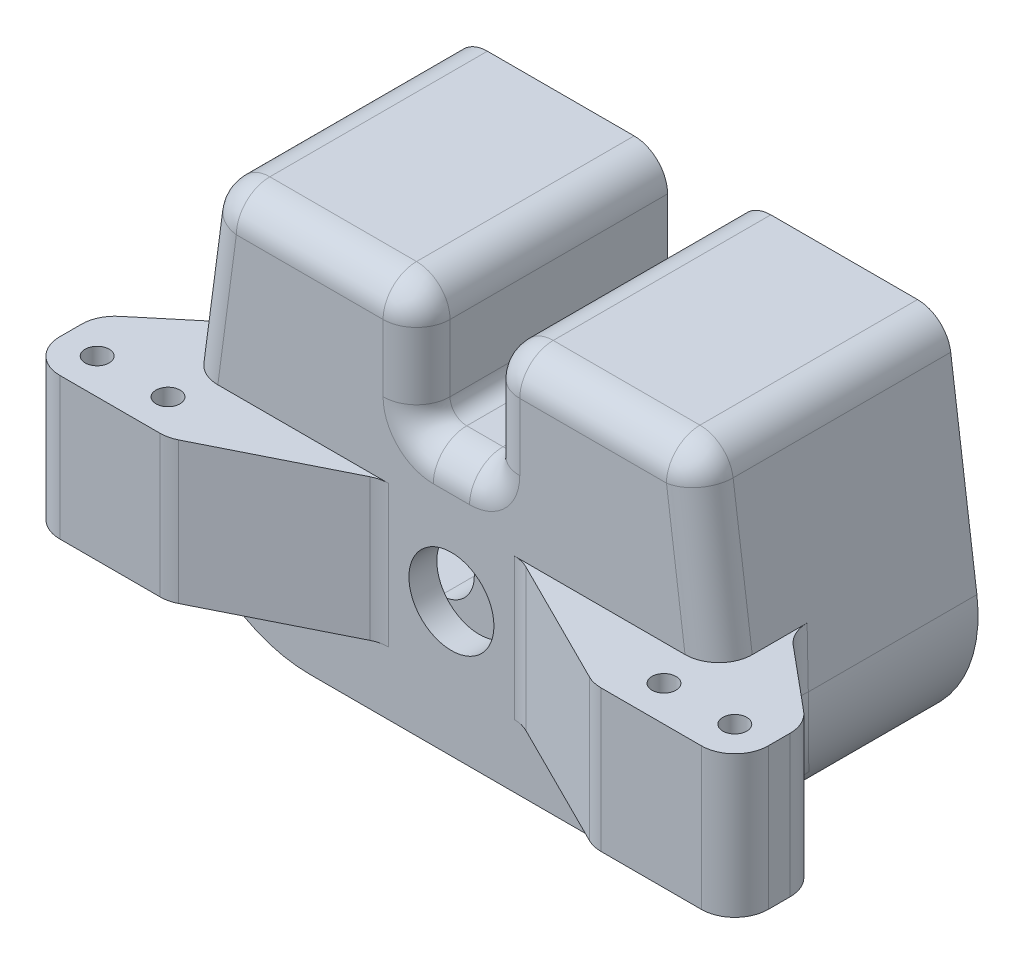
SolidWorks part; units mm, degrees
ref_plane "Front Plane" through (0, 0, 0) normal (0, 0, 1) x (1, 0, 0)
ref_plane "Top Plane" through (0, 0, 0) normal (0, 1, 0) x (1, 0, 0)
ref_plane "Right Plane" through (0, 0, 0) normal (1, 0, 0) x (0, 0, -1)
sketch "Sketch2" plane through (0, 0, 0) normal (0, 0, 1) x (1, 0, 0)
  line L0 (0, -1012.7) -> (0, -6.35) construction
  line L5 (16.9, 15) -> (33.9, 15)
  line L6 (10.9, 9) -> (10.9, -9)
  line L7 (16.9, -15) -> (33.9, -15)
  line L8 (39.9, 9) -> (39.9, -9)
  line L9 (10.9, 15) -> (39.9, -15) construction
  line L10 (10.9, -15) -> (39.9, 15) construction
  line L11 (-25.4, 24) -> (25.4, 24)
  line L12 (12.25, -16.75) -> (38.55, -16.75)
  line L13 (8.65, -13.15) -> (8.65, 37.65)
  line L14 (12.25, 41.25) -> (38.55, 41.25)
  line L15 (42.15, -13.15) -> (42.15, 37.65)
  line L16 (-25.4, -24) -> (25.4, -24)
  line L17 (0, 6.35) -> (0, 76.2) construction
  line L18 (-16.9, -15) -> (-33.9, -15)
  line L19 (-39.9, 9) -> (-39.9, -9)
  line L20 (-16.9, 15) -> (-33.9, 15)
  line L21 (-10.9, 9) -> (-10.9, -9)
  line L22 (-12.25, -16.75) -> (-38.55, -16.75)
  line L23 (-8.65, -13.15) -> (-8.65, 37.65)
  line L24 (-42.15, -13.15) -> (-42.15, 37.65)
  line L25 (-12.25, 41.25) -> (-38.55, 41.25)
  line L26 (-38.55, 43.65) -> (38.55, 43.65)
  line L27 (44.4976, 38.4412) -> (49.1904, 3.1648)
  line L28 (-44.4976, 38.4412) -> (-49.1904, 3.1648)
  line L29 (-25.4, 0) -> (25.4, 0) construction
  line L30 (-25.4, 20) -> (25.4, 20)
  line L31 (-25.4, -20) -> (25.4, -20)
  circle A0 centre (0, 0) radius 6.35
  circle A1 centre (25.4, 0) radius 19.05 construction
  circle A2 centre (-25.4, 0) radius 19.05 construction
  arc A3 (-25.4, 24) -> (-25.4, -24) centre (-25.4, 0) ccw
  arc A5 (25.4, -24) -> (25.4, 24) centre (25.4, 0) ccw
  arc A6 (39.9, 9) -> (33.9, 15) centre (33.9, 9) ccw
  arc A7 (16.9, 15) -> (10.9, 9) centre (16.9, 9) ccw
  arc A8 (16.9, -15) -> (10.9, -9) centre (16.9, -9) cw
  arc A9 (33.9, -15) -> (39.9, -9) centre (33.9, -9) ccw
  arc A10 (42.15, 37.65) -> (38.55, 41.25) centre (38.55, 37.65) ccw
  arc A11 (12.25, 41.25) -> (8.65, 37.65) centre (12.25, 37.65) ccw
  arc A12 (12.25, -16.75) -> (8.65, -13.15) centre (12.25, -13.15) cw
  arc A13 (38.55, -16.75) -> (42.15, -13.15) centre (38.55, -13.15) ccw
  circle A14 centre (25.4, 25.05) radius 4.3
  circle A16 centre (25.4, 26.8) radius 6.5
  circle A17 centre (-25.4, 25.05) radius 4.3
  circle A19 centre (-25.4, 26.8) radius 6.5
  arc A20 (-33.9, -15) -> (-39.9, -9) centre (-33.9, -9) cw
  arc A21 (-39.9, 9) -> (-33.9, 15) centre (-33.9, 9) cw
  arc A22 (-16.9, 15) -> (-10.9, 9) centre (-16.9, 9) cw
  arc A23 (-16.9, -15) -> (-10.9, -9) centre (-16.9, -9) ccw
  arc A24 (-38.55, -16.75) -> (-42.15, -13.15) centre (-38.55, -13.15) cw
  arc A25 (-12.25, -16.75) -> (-8.65, -13.15) centre (-12.25, -13.15) ccw
  arc A26 (-12.25, 41.25) -> (-8.65, 37.65) centre (-12.25, 37.65) cw
  arc A27 (-42.15, 37.65) -> (-38.55, 41.25) centre (-38.55, 37.65) cw
  circle A28 centre (38.55, 37.65) radius 6
  circle A29 centre (-38.55, 37.65) radius 6
  arc A30 (-25.4, 20) -> (-25.4, -20) centre (-25.4, 0) ccw
  arc A31 (25.4, -20) -> (25.4, 20) centre (25.4, 0) ccw
  circle A32 centre (0, 0) radius 2.375
  point P37 (42.15, 41.25)
  point P42 (8.65, -16.75)
  point P45 (42.15, -16.75)
  point P88 (0, 0)
  dimension "D1" = 12.7
  dimension "D2" = 38.1
  dimension "D3" = 38.1
  dimension "D10" = 24
  dimension "D11" = 6
  dimension "D12" = 3.6
  dimension "D14" = 8.6
  dimension "D15" = 4.75
  dimension "D17" = 13
  dimension "D4" = 33.5
  dimension "D5" = 58
  dimension "D6" = 16.75
  dimension "D7" = 16.75
  dimension "D8" = 29
  dimension "D9" = 30
  dimension "D13" = 16.2
  dimension "D16" = 1.75
  dimension "D18" = 2.4
  dimension "D19" = 40
extrude "Boss-Extrude3" add sketch "Sketch2" along normal blind 5 contours L31 A31 L12 A12 L13 L30 L23 A25 L22 A30 A0 | L15 A31 L30 L13 A12 L12 A9 L7 A8 L6 A7 L5 A6 L8 | L30 A30 L24 L22 A25 L23 A23 L18 A20 L19 A21 L20 A22 L21 | L18 A23 L21 A22 L20 A21 L19 A20 | L7 A9 L8 A6 L5 A7 L6 A8 | A31 L31 A30 L22 A24 L24 A3 L16 A5 L15 A13 L12 | L15 A31 | A31 L12 A13 L15 | A30 L24 A24 L22 | L24 A30 | A30 L30 L23 L11 A19 A3 L24 | L23 L30 L13 L11 | A31 L15 A5 A16 L11 L13 L30 | L11 A14 A5 | A5 A16 L11 A14 | A28 L14 A11 L13 L11 A16 A5 L15 | A5 A14 L11 | A17 A3 L11 | A17 L11 A3 | A19 A3 A17 L11 | A19 L11 A17 A3 | A29 L24 A3 A19 L11 L23 A26 L25 | A29 L25 A26 L23 L11 L13 A11 L14 A28 L26 | L24 A29 L25 A27 | L25 A29 L24 A27 | A29 L28 A3 L24 | L14 A28 L15 A10 | A28 L14 A10 L15 | A28 L15 A5 L27 | L11 A16 A5 A14 | A0 A32 region at (25.4, 0, 0) region at (-25.4392, 26.2918, 0) region at (-25.3231, 22.6147, 0) region at (-20.9703, 24.5008, 0) region at (-20.3821, 23.8803, 0) region at (-18.6582, 25.2735, 0) region at (-26.5287, 20.0759, 0) region at (0, 36.2342, 0) region at (0, 22, 0) region at (-44.7431, 22.364, 0) region at (-43.2204, 14.0585, 0) region at (9.0625, 30.825, 0) region at (26.5287, 20.0759, 0) region at (0, 19.1706, 0) region at (-9.1473, 3.425, 0) region at (-43.4595, 0, 0) region at (-43.9413, 35.3863, 0) region at (-37.5571, 36.6571, 0) region at (24.0007, 32.9799, 0) region at (20.3821, 23.8803, 0) region at (17.025, 19.5027, 0) region at (-40.1113, -14.7113, 0) region at (25.4392, 26.2918, 0) region at (25.3231, 22.6147, 0) region at (44.7431, 22.364, 0) region at (43.4595, 0, 0) region at (35.935, 42.88, 0) region at (37.5571, 36.6571, 0) region at (40.1113, -14.7113, 0) region at (-25.4, 0, 0) region at (-6.1704, 0, 0)
extrude "Boss-Extrude4" add sketch "Sketch2<6>" against normal blind 5 contours A31 L15 A5 A16 L11 L13 L30 | L23 L30 L13 L11 | A30 L30 L23 L11 A19 A3 L24 | A31 L31 A30 L22 A24 L24 A3 L16 A5 L15 A13 L12 | A31 L12 A13 L15 | A30 L24 A24 L22 | A29 L25 A26 L23 L11 L13 A11 L14 A28 L26 | A29 L24 A3 A19 L11 L23 A26 L25 | L24 A29 L25 A27 | L25 A29 L24 A27 | A29 L28 A3 L24 | A28 L14 A11 L13 L11 A16 A5 L15 | L14 A28 L15 A10 | A28 L14 A10 L15 | A28 L15 A5 L27 | A5 A16 L11 A14 | A5 A14 L11 | L11 A16 A5 A14 | L11 A14 A5 | A19 L11 A17 A3 | A17 L11 A3 | A17 A3 L11 | A19 A3 A17 L11 region at (-25.4392, 26.2918, 0) region at (-25.3231, 22.6147, 0) region at (-20.9703, 24.5008, 0) region at (-20.3821, 23.8803, 0) region at (-18.6582, 25.2735, 0) region at (-26.5287, 20.0759, 0) region at (0, 36.2342, 0) region at (0, 22, 0) region at (-44.7431, 22.364, 0) region at (-43.2204, 14.0585, 0) region at (9.0625, 30.825, 0) region at (26.5287, 20.0759, 0) region at (-43.9413, 35.3863, 0) region at (-37.5571, 36.6571, 0) region at (24.0007, 32.9799, 0) region at (20.3821, 23.8803, 0) region at (-40.1113, -14.7113, 0) region at (25.4392, 26.2918, 0) region at (25.3231, 22.6147, 0) region at (44.7431, 22.364, 0) region at (35.935, 42.88, 0) region at (37.5571, 36.6571, 0) region at (40.1113, -14.7113, 0)
sketch "Sketch2<6>" plane through (0, 0, 0) normal (0, 0, 1) x (1, 0, 0) same geometry as "Sketch2"
extrude "Boss-Extrude5" add sketch "Sketch2<7>" against normal blind 5 from surface contours A5 A16 L11 A14 | L11 A16 A5 A14 | A31 L15 A5 A16 L11 L13 L30 | A28 L14 A11 L13 L11 A16 A5 L15 | L14 A28 L15 A10 | A28 L14 A10 L15 | A29 L25 A26 L23 L11 L13 A11 L14 A28 L26 | A29 L24 A3 A19 L11 L23 A26 L25 | A30 L30 L23 L11 A19 A3 L24 | L23 L30 L13 L11 | A19 A3 A17 L11 | A19 L11 A17 A3 | L24 A29 L25 A27 | L25 A29 L24 A27 | A29 L28 A3 L24 | A28 L15 A5 L27 | A30 L24 A24 L22 | A31 L31 A30 L22 A24 L24 A3 L16 A5 L15 A13 L12 | A31 L12 A13 L15 | A5 A14 L11 | L11 A14 A5 | A17 A3 L11 | A17 L11 A3 region at (-25.4392, 26.2918, 0) region at (-25.3231, 22.6147, 0) region at (-20.9703, 24.5008, 0) region at (-20.3821, 23.8803, 0) region at (-18.6582, 25.2735, 0) region at (-26.5287, 20.0759, 0) region at (0, 36.2342, 0) region at (0, 22, 0) region at (-44.7431, 22.364, 0) region at (-43.2204, 14.0585, 0) region at (9.0625, 30.825, 0) region at (26.5287, 20.0759, 0) region at (-43.9413, 35.3863, 0) region at (-37.5571, 36.6571, 0) region at (24.0007, 32.9799, 0) region at (20.3821, 23.8803, 0) region at (-40.1113, -14.7113, 0) region at (25.4392, 26.2918, 0) region at (25.3231, 22.6147, 0) region at (44.7431, 22.364, 0) region at (35.935, 42.88, 0) region at (37.5571, 36.6571, 0) region at (40.1113, -14.7113, 0) starting at face at (0, 14.2449, -5)
sketch "Sketch2<7>" plane through (0, 0, 0) normal (0, 0, 1) x (1, 0, 0) same geometry as "Sketch2"
extrude "Boss-Extrude6" add sketch "Sketch2<8>" against normal blind 11 from surface contours L15 A31 L30 L13 A12 L12 A9 L7 A8 L6 A7 L5 A6 L8 | L31 A31 L12 A12 L13 L30 L23 A25 L22 A30 A0 | L30 A30 L24 L22 A25 L23 A23 L18 A20 L19 A21 L20 A22 L21 | A31 L31 A30 L22 A24 L24 A3 L16 A5 L15 A13 L12 | A30 L24 A24 L22 | A29 L24 A3 A19 L11 L23 A26 L25 | A31 L15 A5 A16 L11 L13 L30 | L15 A31 | L24 A30 | L23 L30 L13 L11 | A30 L30 L23 L11 A19 A3 L24 | A28 L14 A11 L13 L11 A16 A5 L15 | A29 L25 A26 L23 L11 L13 A11 L14 A28 L26 | L24 A29 L25 A27 | L25 A29 L24 A27 | A29 L28 A3 L24 | L14 A28 L15 A10 | A28 L14 A10 L15 | A28 L15 A5 L27 | A31 L12 A13 L15 | A19 A3 A17 L11 | A5 A16 L11 A14 | L11 A16 A5 A14 | A19 L11 A17 A3 | A0 A32 region at (-20.9703, 24.5008, 0) region at (-20.3821, 23.8803, 0) region at (-18.6582, 25.2735, 0) region at (-26.5287, 20.0759, 0) region at (0, 36.2342, 0) region at (0, 22, 0) region at (-44.7431, 22.364, 0) region at (-43.2204, 14.0585, 0) region at (9.0625, 30.825, 0) region at (26.5287, 20.0759, 0) region at (0, 19.1706, 0) region at (-9.1473, 3.425, 0) region at (-43.4595, 0, 0) region at (-43.9413, 35.3863, 0) region at (-37.5571, 36.6571, 0) region at (24.0007, 32.9799, 0) region at (20.3821, 23.8803, 0) region at (17.025, 19.5027, 0) region at (-40.1113, -14.7113, 0) region at (44.7431, 22.364, 0) region at (43.4595, 0, 0) region at (35.935, 42.88, 0) region at (37.5571, 36.6571, 0) region at (40.1113, -14.7113, 0) region at (-6.1704, 0, 0) starting at face at (0, 14.2449, -10)
sketch "Sketch2<8>" plane through (0, 0, 0) normal (0, 0, 1) x (1, 0, 0) same geometry as "Sketch2"
extrude "Boss-Extrude7" add sketch "Sketch2<9>" against normal blind 4 from surface contours L31 A31 L12 A12 L13 L30 L23 A25 L22 A30 A0 | L30 A30 L24 L22 A25 L23 A23 L18 A20 L19 A21 L20 A22 L21 | L24 A30 | L15 A31 L30 L13 A12 L12 A9 L7 A8 L6 A7 L5 A6 L8 | L15 A31 | A31 L31 A30 L22 A24 L24 A3 L16 A5 L15 A13 L12 | A31 L12 A13 L15 | A30 L24 A24 L22 | A29 L28 A3 L24 | A30 L30 L23 L11 A19 A3 L24 | L23 L30 L13 L11 | A31 L15 A5 A16 L11 L13 L30 | A28 L14 A11 L13 L11 A16 A5 L15 | A28 L15 A5 L27 | L14 A28 L15 A10 | A28 L14 A10 L15 | A29 L25 A26 L23 L11 L13 A11 L14 A28 L26 | A29 L24 A3 A19 L11 L23 A26 L25 | L24 A29 L25 A27 | L25 A29 L24 A27 | A0 A32 region at (-18.6582, 25.2735, 0) region at (-26.5287, 20.0759, 0) region at (0, 36.2342, 0) region at (0, 22, 0) region at (-44.7431, 22.364, 0) region at (-43.2204, 14.0585, 0) region at (9.0625, 30.825, 0) region at (26.5287, 20.0759, 0) region at (0, 19.1706, 0) region at (-9.1473, 3.425, 0) region at (-43.4595, 0, 0) region at (-43.9413, 35.3863, 0) region at (-37.5571, 36.6571, 0) region at (17.025, 19.5027, 0) region at (-40.1113, -14.7113, 0) region at (44.7431, 22.364, 0) region at (43.4595, 0, 0) region at (35.935, 42.88, 0) region at (37.5571, 36.6571, 0) region at (40.1113, -14.7113, 0) region at (-6.1704, 0, 0) starting at face at (2.375, 0, -21)
sketch "Sketch2<9>" plane through (0, 0, 0) normal (0, 0, 1) x (1, 0, 0) same geometry as "Sketch2"
extrude "Boss-Extrude8" add sketch "Sketch2<10>" against normal blind 15 from surface contours A28 L15 A5 L27 | A28 L14 A10 L15 | A29 L25 A26 L23 L11 L13 A11 L14 A28 L26 | L25 A29 L24 A27 | L31 A31 L12 A12 L13 L30 L23 A25 L22 A30 A0 | L23 L30 L13 L11 | A31 L31 A30 L22 A24 L24 A3 L16 A5 L15 A13 L12 | A29 L28 A3 L24 | L24 A30 | L15 A31 | A0 A32 region at (0, 36.2342, 0) region at (0, 22, 0) region at (-44.7431, 22.364, 0) region at (-43.2204, 14.0585, 0) region at (0, 19.1706, 0) region at (-43.4595, 0, 0) region at (-43.9413, 35.3863, 0) region at (44.7431, 22.364, 0) region at (43.4595, 0, 0) region at (35.935, 42.88, 0) region at (-6.1704, 0, 0) starting at face at (2.375, 0, -25)
sketch "Sketch2<10>" plane through (0, 0, 0) normal (0, 0, 1) x (1, 0, 0) same geometry as "Sketch2"
sketch "Sketch3" plane through (0, 0, 0) normal (0, 0, 1) x (1, 0, 0)
  line L5 (-63.5, 12.7) -> (63.5, 12.7)
  line L6 (-63.5, 12.7) -> (-63.5, -12.7)
  line L7 (-63.5, -12.7) -> (63.5, -12.7)
  line L8 (63.5, 12.7) -> (63.5, -12.7)
  circle A0 centre (0, 0) radius 2
  point P0 (0, 0)
  dimension "D5" = 4
  dimension "D1" = 25.4
  dimension "D2" = 127
  dimension "D3" = 12.7
  dimension "D4" = 63.5
extrude "Boss-Extrude9" add sketch "Sketch3" along normal blind 12.7 from surface starting at face at (0, 14.2449, 5)
sketch "Sketch4" plane through (0, 12.7, 0) normal (0, 1, 0) x (1, 0, 0)
  line L0 (-38.1, -17.7) -> (-12.7, -5)
  line L1 (-63.5, -5) -> (63.5, -5)
  line L2 (-63.5, -5) -> (-63.5, -17.7)
  line L3 (-63.5, -17.7) -> (63.5, -17.7)
  line L4 (63.5, -5) -> (63.5, -17.7)
  line L5 (12.7, -5) -> (38.1, -17.7)
  line L6 (0, 0) -> (0, -29.8353) construction
  line L7 (-63.5, -5) -> (-45.5, 10)
  line L8 (-45.5, 10) -> (-45.5, -5)
  line L9 (63.5, -5) -> (45.5, 10)
  line L10 (45.5, 10) -> (45.5, -5)
  circle A0 centre (-57.15, -11.35) radius 2.15
  circle A1 centre (-44.45, -11.35) radius 2.15
  circle A2 centre (44.45, -11.35) radius 2.15
  circle A3 centre (57.15, -11.35) radius 2.15
  line M5 (-47.922, -5) -> (-63.5, -5)
  line M7 (-63.5, -17.7) -> (63.5, -17.7)
  line M9 (63.5, -5) -> (47.922, -5)
  line M10 (47.922, -5) -> (-47.922, -5)
  dimension "D7" = 4.3
  dimension "D9" = 4.3
  dimension "D1" = 25.4
  dimension "D2" = 25.4
  dimension "D3" = 50.8
  dimension "D4" = 50.8
  dimension "D5" = 6.35
  dimension "D6" = 6.35
  dimension "D8" = 12.7
  dimension "D10" = 18
  dimension "D11" = 15
  dimension "D12" = 18
  dimension "D13" = 15
extrude "Cut-Extrude1" cut sketch "Sketch4" against normal up to next contours L6 L0 M10 M7 | L1 L6 L3 L5 | A0 | A1 | A3 | A2 region at (-13.7583, 12.7, 12.4083) region at (13.7583, 12.7, 12.4083) region at (-57.15, 12.7, 11.35) region at (-44.45, 12.7, 11.35) region at (44.45, 12.7, 11.35) region at (57.15, 12.7, 11.35)
sketch "Sketch8" plane through (0, 0, 5) normal (0, 0, 1) x (1, 0, 0)
  circle A0 centre (0, 0) radius 7.62
  dimension "D1" = 15.24
extrude "Boss-Extrude12" add sketch "Sketch4<3>" against normal up to surface (25.4 mm away) contours L8 L7 L1 M5 | L9 L10 M10 M9 region at (-51.5, 12.7, 0) region at (51.5, 12.7, 0) up to face at (-44.45, -12.7, 9.2)
sketch "Sketch4<3>" plane through (0, 12.7, 0) normal (0, 1, 0) x (1, 0, 0) same geometry as "Sketch4"
extrude "Cut-Extrude3" cut sketch "Sketch8" against normal up to next
fillet "Fillet3" radius 6 12 edges at (-48.8592, -5.066, -7.2006) (48.5562, 7.9324, -7.4532) (-48.5562, 7.9324, -7.4532) (-63.5, 0, 5) (48.8592, -5.066, -7.2006) (63.5, 0, 5) (63.5, 0, 17.7) (12.7, 0, 5) (38.1, 0, 17.7) (-63.5, 0, 17.7) (-12.7, 0, 5) (-38.1, 0, 17.7)
ref_plane "Plane5" through (0, -20, 0) normal (0, 1, 0) x (1, 0, 0)
sketch "Sketch9" plane through (0, -20, 0) normal (0, 1, 0) x (1, 0, 0)
  line L1 (35, 0) -> (-35, 0)
  line L2 (35, 0) -> (35, 10)
  line L3 (35, 10) -> (-35, 10)
  line L4 (-35, 0) -> (-35, 10)
  line L5 (-25.4, 0) -> (25.4, 0) construction
  point P8 (0, 0)
  dimension "D1" = 10
  dimension "D2" = 70
  dimension "D3" = 10
  dimension "D4" = 35
extrude "Cut-Extrude4" cut sketch "Sketch9" against normal through all and the other way blind 5
fillet "Fillet4" radius 3 4 edges at (35, -19.7709, -10) (35, -19.7709, 0) (-35, -19.7709, -10) (-35, -19.7709, 0)
fillet "Fillet5" radius 1 2 edges at (29.7, 25.05, -10) (-21.1, 25.05, -10)
fillet "Fillet6" radius 1 3 edges at (45.1179, 3.3472, -10) (0, 20, -10) (-45.1179, 3.3472, -10)
fillet "Fillet7" radius 1 3 edges at (45.1179, 3.3472, 0) (0, 20, 0) (-45.1179, 3.3472, 0)
ref_plane "Plane6" through (0, 0, 5) normal (0, 0, 1) x (1, 0, 0)
sketch "Sketch10" plane through (0, 0, 5) normal (0, 0, 1) x (1, 0, 0)
  line L0 (-38.55, 43.65) -> (-12.25, 43.65)
  line L1 (8.65, -13.15) -> (8.65, 37.65) construction
  line L3 (-6.25, 37.65) -> (-6.25, 25.65)
  line L4 (-3.25, 22.65) -> (3.25, 22.65)
  line L5 (6.25, 37.65) -> (6.25, 25.65)
  line L6 (12.25, 41.25) -> (38.55, 41.25) construction
  line L7 (42.15, 37.65) -> (42.15, -13.15) construction
  line L8 (38.55, -16.75) -> (12.25, -16.75) construction
  line L9 (-42.15, -13.15) -> (-42.15, 37.65) construction
  line L10 (-38.55, 41.25) -> (-12.25, 41.25) construction
  line L11 (-8.65, 37.65) -> (-8.65, -13.15) construction
  line L12 (-12.25, -16.75) -> (-38.55, -16.75) construction
  line L13 (8.65, -13.15) -> (8.65, 37.65)
  line L14 (12.25, 41.25) -> (38.55, 41.25)
  line L15 (42.15, 37.65) -> (42.15, -13.15)
  line L16 (38.55, -16.75) -> (12.25, -16.75)
  line L17 (-42.15, -13.15) -> (-42.15, 37.65)
  line L18 (-38.55, 41.25) -> (-12.25, 41.25)
  line L19 (-8.65, 37.65) -> (-8.65, -13.15)
  line L20 (-12.25, -16.75) -> (-38.55, -16.75)
  line L21 (12.25, 43.65) -> (38.55, 43.65)
  line L22 (-12.25, 43.65) -> (12.25, 43.65)
  arc A0 (8.65, -13.15) -> (12.25, -16.75) centre (12.25, -13.15) ccw construction
  arc A1 (12.25, 41.25) -> (8.65, 37.65) centre (12.25, 37.65) ccw construction
  arc A2 (42.15, 37.65) -> (38.55, 41.25) centre (38.55, 37.65) ccw construction
  arc A3 (38.55, -16.75) -> (42.15, -13.15) centre (38.55, -13.15) ccw construction
  arc A4 (-42.15, -13.15) -> (-38.55, -16.75) centre (-38.55, -13.15) ccw construction
  arc A5 (-38.55, 41.25) -> (-42.15, 37.65) centre (-38.55, 37.65) ccw construction
  arc A6 (-8.65, 37.65) -> (-12.25, 41.25) centre (-12.25, 37.65) ccw construction
  arc A7 (-12.25, -16.75) -> (-8.65, -13.15) centre (-12.25, -13.15) ccw construction
  arc A8 (8.65, -13.15) -> (12.25, -16.75) centre (12.25, -13.15) ccw
  arc A9 (12.25, 41.25) -> (8.65, 37.65) centre (12.25, 37.65) ccw
  arc A10 (42.15, 37.65) -> (38.55, 41.25) centre (38.55, 37.65) ccw
  arc A11 (38.55, -16.75) -> (42.15, -13.15) centre (38.55, -13.15) ccw
  arc A12 (-42.15, -13.15) -> (-38.55, -16.75) centre (-38.55, -13.15) ccw
  arc A13 (-38.55, 41.25) -> (-42.15, 37.65) centre (-38.55, 37.65) ccw
  arc A14 (-8.65, 37.65) -> (-12.25, 41.25) centre (-12.25, 37.65) ccw
  arc A15 (-12.25, -16.75) -> (-8.65, -13.15) centre (-12.25, -13.15) ccw
  arc A16 (-6.25, 37.65) -> (-12.25, 43.65) centre (-12.25, 37.65) ccw
  arc A17 (12.25, 43.65) -> (6.25, 37.65) centre (12.25, 37.65) ccw
  arc A18 (3.25, 22.65) -> (6.25, 25.65) centre (3.25, 25.65) ccw
  arc A19 (-3.25, 22.65) -> (-6.25, 25.65) centre (-3.25, 25.65) cw
  dimension "D4" = 6
  dimension "D5" = 6
  dimension "D6" = 3
  dimension "D1" = 2.4
  dimension "D2" = 2.4
  dimension "D3" = 21
extrude "Cut-Extrude5" cut sketch "Sketch10" against normal up to next contours A19 L4 A18 L5 A17 L22 A16 L3 region at (0, 33.8049, 5)
ref_plane "Plane7" through (-63.5, 0, 0) normal (-1, 0, 0) x (0, 0, 1)
sketch "Sketch11" plane through (-63.5, 0, 0) normal (-1, 0, 0) x (0, 0, 1)
  line L0 (5, 12.7) -> (5, 43.65)
  line L1 (5, 43.65) -> (-12, 43.65)
  line L2 (5, 43.65) -> (-40, 43.65) construction
  line L3 (-12, 43.65) -> (5, 22.65)
  dimension "D1" = 17
fillet "Fillet9" radius 6 12 edges at (46.2098, 25.5706, 5) (42.503, 42.1637, 5) (-25.4, 43.65, 5) (8.0074, 41.8926, 5) (6.25, 31.65, 5) (5.3713, 23.5287, 5) (0, 22.65, 5) (-5.3713, 23.5287, 5) (-6.25, 31.65, 5) (-8.0074, 41.8926, 5) (-42.503, 42.1637, 5) (-46.2098, 25.5706, 5)
